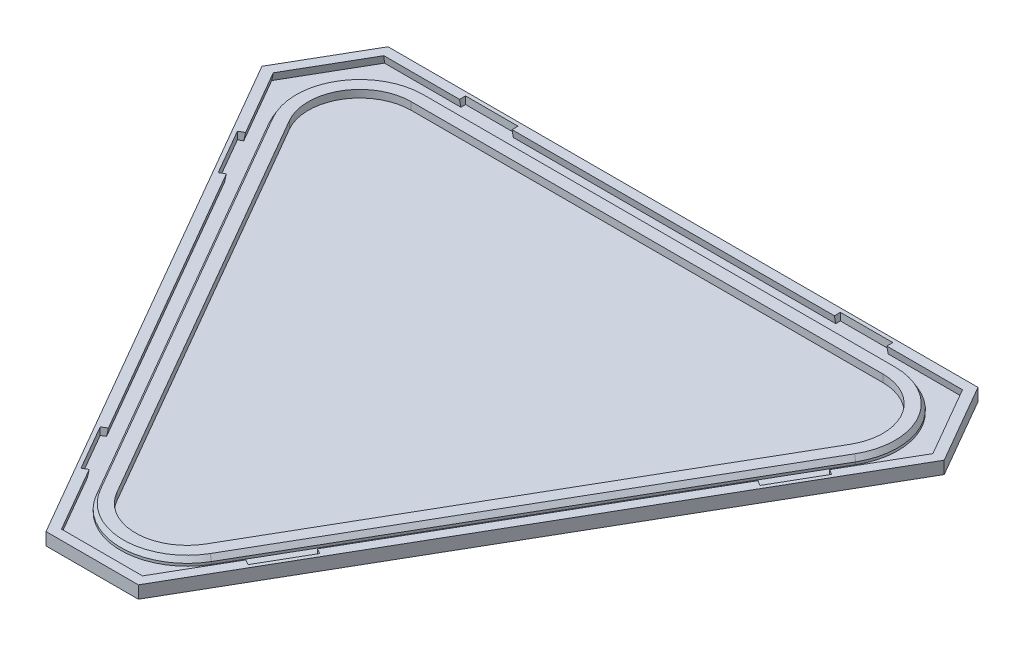
SolidWorks part; units mm, degrees
ref_plane "Plan de face" through (0, 0, 0) normal (0, 0, 1) x (1, 0, 0)
ref_plane "Plan de dessus" through (0, 0, 0) normal (0, 1, 0) x (1, 0, 0)
ref_plane "Plan de droite" through (0, 0, 0) normal (1, 0, 0) x (0, 0, -1)
sketch "Esquisse2" plane through (0, 0, 0) normal (0, 1, 0) x (1, 0, 0)
  line L3 (-59.0248, 44.7446) -> (-68.2624, 28.7446) construction
  line L4 (-59.0248, 44.7446) -> (59.0248, 44.7446) construction
  line L5 (68.2624, 28.7446) -> (9.2376, -73.4893) construction
  line L6 (-68.2624, 28.7446) -> (-59.0248, 44.7446)
  line L7 (59.0248, 44.7446) -> (68.2624, 28.7446)
  line L8 (9.2376, -73.4893) -> (-9.2376, -73.4893)
  line L9 (-68.2624, 28.7446) -> (-9.2376, -73.4893)
  line L10 (9.2376, -73.4893) -> (68.2624, 28.7446)
  line L11 (59.0248, 44.7446) -> (-59.0248, 44.7446)
  line L12 (-9.2376, -73.4893) -> (-68.2624, 28.7446) construction
  line L13 (-9.2376, -73.4893) -> (9.2376, -73.4893) construction
  line L14 (68.2624, 28.7446) -> (59.0248, 44.7446) construction
  point P16 (0, 0)
extrude "Boss.-Extru.2" add sketch "Esquisse2" along normal blind 1
sketch "Esquisse5" plane through (0, 1, 0) normal (0, 1, 0) x (1, 0, 0)
  line L19 (-68.2624, 28.7446) -> (-9.2376, -73.4893)
  line L20 (-9.2376, -73.4893) -> (9.2376, -73.4893)
  line L21 (9.2376, -73.4893) -> (68.2624, 28.7446)
  line L26 (68.2624, 28.7446) -> (59.0248, 44.7446)
  line L27 (59.0248, 44.7446) -> (-59.0248, 44.7446)
  line L32 (-59.0248, 44.7446) -> (-68.2624, 28.7446)
  line L37 (-68.2624, 28.7446) -> (-9.2376, -73.4893)
  line L38 (-9.2376, -73.4893) -> (9.2376, -73.4893)
  line L39 (9.2376, -73.4893) -> (68.2624, 28.7446)
  line L44 (68.2624, 28.7446) -> (59.0248, 44.7446)
  line L45 (59.0248, 44.7446) -> (-59.0248, 44.7446)
  line L50 (-59.0248, 44.7446) -> (-68.2624, 28.7446)
  dimension "D1" = 0
extrude "Extru.-Mince1" add sketch "Esquisse5" along normal blind 1.5 draft 10 thin draft outward yes thin type one direction reverse wall 1.7
sketch "Esquisse6" plane through (0, 0, 0) normal (0, -1, 0) x (1, 0, 0)
  line L6 (-59.0248, -44.7446) -> (59.0248, -44.7446)
  line L7 (59.0248, -44.7446) -> (68.2624, -28.7446)
  line L8 (68.2624, -28.7446) -> (9.2376, 73.4893)
  line L9 (9.2376, 73.4893) -> (-9.2376, 73.4893)
  line L10 (-9.2376, 73.4893) -> (-68.2624, -28.7446)
  line L11 (-68.2624, -28.7446) -> (-59.0248, -44.7446)
  line L12 (-59.0248, -44.7446) -> (59.0248, -44.7446)
  line L13 (59.0248, -44.7446) -> (68.2624, -28.7446)
  line L14 (68.2624, -28.7446) -> (9.2376, 73.4893)
  line L15 (9.2376, 73.4893) -> (-9.2376, 73.4893)
  line L16 (-9.2376, 73.4893) -> (-68.2624, -28.7446)
  line L17 (-68.2624, -28.7446) -> (-59.0248, -44.7446)
  dimension "D1" = 0
extrude "Enlèv. de mat.-Extru.-Mince1" cut sketch "Esquisse6" against normal through all thin thin type one direction wall 1.5
sketch "Esquisse7" plane through (0, 1, 0) normal (0, 1, 0) x (1, 0, 0)
  line L0 (2.25, 44.7446) -> (-2.25, 44.7446)
  line L1 (2.25, 44.7446) -> (2.25, 40.6446)
  line L2 (-2.25, 44.7446) -> (-2.25, 40.6446)
  line L3 (2.25, 40.6446) -> (-2.25, 40.6446)
  line L4 (-59.0248, 44.7446) -> (59.0248, 44.7446) construction
  line L5 (34.0743, -22.2709) -> (36.3243, -18.3738)
  line L6 (37.625, -24.3209) -> (34.0743, -22.2709)
  line L7 (37.625, -24.3209) -> (39.875, -20.4238)
  line L8 (39.875, -20.4238) -> (36.3243, -18.3738)
  line L9 (-36.3243, -18.3738) -> (-34.0743, -22.2709)
  line L10 (-39.875, -20.4238) -> (-36.3243, -18.3738)
  line L11 (-39.875, -20.4238) -> (-37.625, -24.3209)
  line L12 (-37.625, -24.3209) -> (-34.0743, -22.2709)
  point P6 (0, 44.7446)
  point P7 (0, 44.7446)
  point P19 (0, 0)
  dimension "D1" = 4.1
  dimension "D2" = 4.5
  dimension "D3" = 3
extrude "Boss.-Extru.5" [suppressed] add sketch "Esquisse7" along normal up to surface (1.5 mm away)
sketch "Esquisse8" [suppressed] plane through (0, 1, 0) normal (0, 1, 0) x (1, 0, 0)
  line L0 (-2.25, 40.6446) -> (2.25, 40.6446) construction
  line L1 (-5, 40.6446) -> (5, 40.6446)
  line L2 (-5, 40.6446) -> (-5, 38.6446)
  line L3 (-5, 38.6446) -> (5, 38.6446)
  line L4 (5, 40.6446) -> (5, 38.6446)
  line L5 (37.6993, -15.9922) -> (32.6993, -24.6524)
  line L6 (37.6993, -15.9922) -> (35.9672, -14.9922)
  line L7 (35.9672, -14.9922) -> (30.9672, -23.6524)
  line L8 (32.6993, -24.6524) -> (30.9672, -23.6524)
  line L9 (-32.6993, -24.6524) -> (-37.6993, -15.9922)
  line L10 (-32.6993, -24.6524) -> (-30.9672, -23.6524)
  line L11 (-30.9672, -23.6524) -> (-35.9672, -14.9922)
  line L12 (-37.6993, -15.9922) -> (-35.9672, -14.9922)
  point P7 (0, 40.6446)
  point P8 (0, 40.6446)
  point P18 (0, 0)
  dimension "D1" = 10
  dimension "D2" = 2
  dimension "D3" = 3
extrude "Boss.-Extru.6" [suppressed] add sketch "Esquisse8" along normal blind 2.2
sketch "Esquisse9" [suppressed] plane through (0, 3.2, 0) normal (0, 1, 0) x (1, 0, 0)
  line L1 (0.6, 40.9446) -> (-0.6, 40.9446)
  line L2 (0.6, 40.9446) -> (0.6, 38.6446)
  line L3 (0.6, 38.6446) -> (-0.6, 38.6446)
  line L4 (-0.6, 40.9446) -> (-0.6, 38.6446)
  line L6 (35.1591, -20.9919) -> (35.7591, -19.9527)
  line L7 (35.1591, -20.9919) -> (33.1672, -19.8419)
  line L8 (33.1672, -19.8419) -> (33.7672, -18.8027)
  line L9 (35.7591, -19.9527) -> (33.7672, -18.8027)
  line L10 (-35.7591, -19.9527) -> (-35.1591, -20.9919)
  line L11 (-35.7591, -19.9527) -> (-33.7672, -18.8027)
  line L12 (-33.7672, -18.8027) -> (-33.1672, -19.8419)
  line L13 (-35.1591, -20.9919) -> (-33.1672, -19.8419)
  line L14 (-2.25, 40.6446) -> (2.25, 40.6446) construction
  line L15 (5, 40.6446) -> (-5, 40.6446) construction
  line L16 (-5, 38.6446) -> (5, 38.6446) construction
  point P4 (0, 40.9446)
  point P9 (0, 40.6446)
  point P21 (0, 0)
  dimension "D1" = 1.2
  dimension "D2" = 3
  dimension "D3" = 0.3
extrude "Boss.-Extru.7" [suppressed] add sketch "Esquisse9" along normal blind 3 and the other way up to next
sketch "Esquisse10" plane through (0, 2.5, 0) normal (0, 1, 0) x (1, 0, 0)
  line L0 (0, 44.7446) -> (0, 32.7785) construction
  line L1 (-32.25, 43.9802) -> (-42.75, 43.9802)
  line L2 (-32.25, 43.9802) -> (-32.25, 39.7025)
  line L3 (-32.25, 39.7025) -> (-42.75, 39.7025)
  line L4 (-42.75, 43.9802) -> (-42.75, 39.7025)
  line L5 (57.8906, 42.7802) -> (-57.8906, 42.7802) construction
  line L7 (-59.0248, 44.7446) -> (59.0248, 44.7446) construction
  line L8 (42.75, 43.9802) -> (42.75, 39.7025)
  line L9 (32.25, 39.7025) -> (42.75, 39.7025)
  line L10 (32.25, 43.9802) -> (32.25, 39.7025)
  line L11 (32.25, 43.9802) -> (42.75, 43.9802)
  line L12 (54.2129, 5.9392) -> (59.4629, 15.0325)
  line L13 (54.2129, 5.9392) -> (50.5084, 8.0781)
  line L14 (50.5084, 8.0781) -> (55.7584, 17.1713)
  line L15 (59.4629, 15.0325) -> (55.7584, 17.1713)
  line L16 (16.7129, -59.0127) -> (13.0084, -56.8738)
  line L17 (18.2584, -47.7806) -> (13.0084, -56.8738)
  line L18 (21.9629, -49.9194) -> (18.2584, -47.7806)
  line L19 (21.9629, -49.9194) -> (16.7129, -59.0127)
  line L20 (-21.9629, -49.9194) -> (-16.7129, -59.0127)
  line L21 (-21.9629, -49.9194) -> (-18.2584, -47.7806)
  line L22 (-18.2584, -47.7806) -> (-13.0084, -56.8738)
  line L23 (-16.7129, -59.0127) -> (-13.0084, -56.8738)
  line L24 (-59.4629, 15.0325) -> (-55.7584, 17.1713)
  line L25 (-50.5084, 8.0781) -> (-55.7584, 17.1713)
  line L26 (-54.2129, 5.9392) -> (-50.5084, 8.0781)
  line L27 (-54.2129, 5.9392) -> (-59.4629, 15.0325)
  point P11 (-37.5, 43.9802)
  point P35 (0, 0)
  dimension "D1" = 1.2
  dimension "D2" = 10.5
  dimension "D3" = 75
  dimension "D4" = 3
extrude "Enlèv. mat.-Extru.1" cut sketch "Esquisse10" against normal up to surface (1.5 mm away) up to face at (0, 1, 0)
sketch "Esquisse11" plane through (0, 1, 0) normal (0, 1, 0) x (1, 0, 0)
  line L9 (11.5181, -61.1393) -> (58.7072, 20.5946)
  line L10 (-58.7072, 20.5946) -> (-11.5181, -61.1393)
  line L11 (47.1891, 40.5446) -> (-47.1891, 40.5446)
  line L12 (11.5181, -61.1393) -> (58.7072, 20.5946)
  line L13 (-58.7072, 20.5946) -> (-11.5181, -61.1393)
  line L14 (47.1891, 40.5446) -> (-47.1891, 40.5446)
  arc A6 (58.7072, 20.5946) -> (47.1891, 40.5446) centre (47.1891, 27.2446) ccw
  arc A7 (-11.5181, -61.1393) -> (11.5181, -61.1393) centre (0, -54.4893) ccw
  arc A8 (-47.1891, 40.5446) -> (-58.7072, 20.5946) centre (-47.1891, 27.2446) ccw
  arc A9 (58.7072, 20.5946) -> (47.1891, 40.5446) centre (47.1891, 27.2446) ccw
  arc A10 (-11.5181, -61.1393) -> (11.5181, -61.1393) centre (0, -54.4893) ccw
  arc A11 (-47.1891, 40.5446) -> (-58.7072, 20.5946) centre (-47.1891, 27.2446) ccw
  dimension "D1" = 0.7
extrude "Extru.-Mince2" add sketch "Esquisse11" along normal up to surface (1.5 mm away) separate body thin up to face at (0, 2.5, 0) thin type one direction reverse wall 3
sketch "Esquisse12" plane through (0, 1, 0) normal (0, 1, 0) x (1, 0, 0)
  line L0 (47.1891, 37.5446) -> (-47.1891, 37.5446) construction
  line L1 (-7.5, 40.7446) -> (7.5, 40.7446)
  line L2 (-7.5, 40.7446) -> (-7.5, 37.5446)
  line L3 (-7.5, 37.5446) -> (7.5, 37.5446)
  line L4 (7.5, 40.7446) -> (7.5, 37.5446)
  line L5 (-7.5, 35.7446) -> (-7.5, 40.7446) construction
  line L6 (7.5, 40.7446) -> (7.5, 35.7446) construction
  line L7 (1.75, 40.7446) -> (9.5, 40.7446) construction
  dimension "D1" = 0
  dimension "D2" = 0
  dimension "D3" = 0
extrude "Boss.-Extru.8" [suppressed] add sketch "Esquisse12" along normal blind 2
ref_axis "Axe1" through (0, 0, 0) along (0, 1, 0)
pattern_circular "Répétition circulaire1" [suppressed] count 3 over 360 about axis through (0, 0, 0) along (0, 1, 0) of bodies 113
chamfer "Chanfrein2" [suppressed] distance 0.5 angle 45
chamfer "Chanfrein1" distance 1 angle 30 6 edges at (-58.7072, 2.5, -33.8946) (58.7072, 2.5, -33.8946) (0, 2.5, 67.7893) (35.1127, 2.5, 20.2723) (-35.1127, 2.5, 20.2723) (0, 2.5, -40.5446) first distance on face at (-55.8277, 1.75, -32.2321) first distance on face at (55.8277, 1.75, -32.2321) first distance on face at (0, 1.75, 64.4643) first distance on face at (35.1127, 1.75, 20.2723) first distance on face at (-35.1127, 1.75, 20.2723) first distance on face at (0, 1.75, -40.5446)
